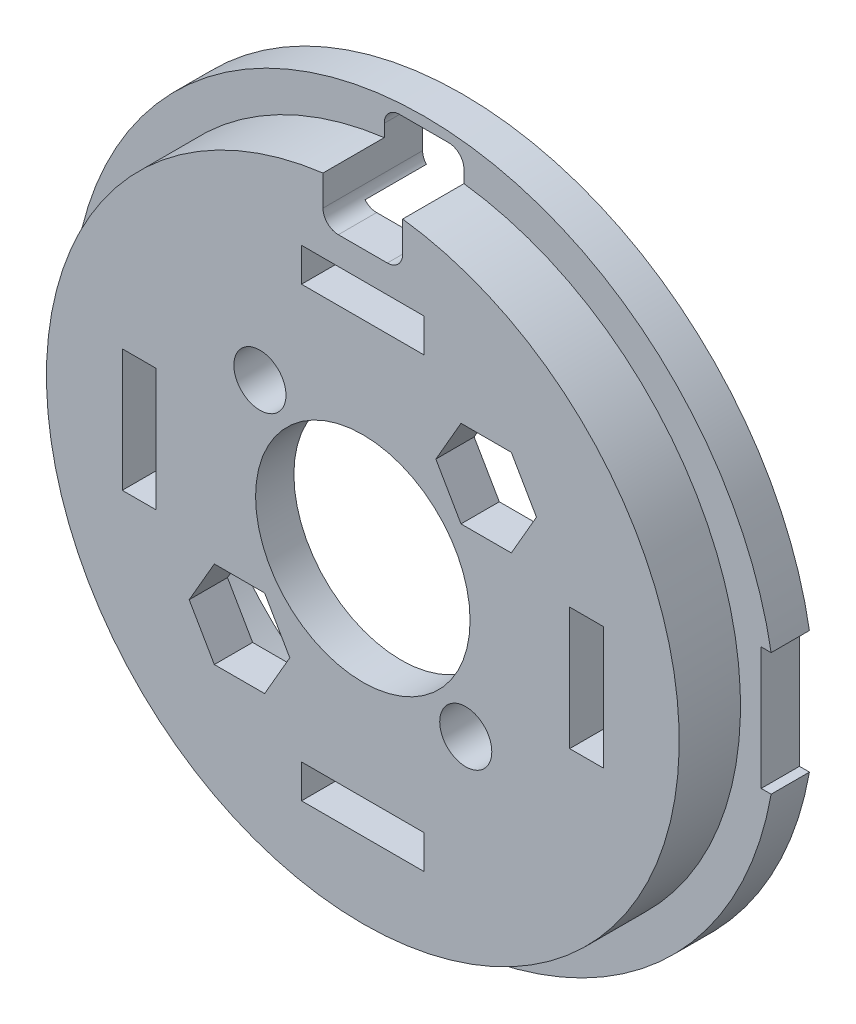
SolidWorks part; units mm, degrees
other "标注1"
sketch "草图10" plane through (17.4, 17.4, 7.6) normal (0.4476, 0.4282, 0.7851) x (0.8625, 0.025, -0.5054)
ref_plane "前视基准面" through (0, 0, 0) normal (0, 0, 1) x (1, 0, 0)
ref_plane "上视基准面" through (0, 0, 0) normal (0, 1, 0) x (1, 0, 0)
ref_plane "右视基准面" through (0, 0, 0) normal (1, 0, 0) x (0, 0, -1)
other "Configuration Table"
sketch "草图1" plane through (0, 0, 0) normal (0, 0, 1) x (1, 0, 0)
  circle A0 centre (0, 0) radius 17.4
  dimension "D1" = 34.8
extrude "凸台-拉伸1" add sketch "草图1" along normal blind 5.6
sketch "草图2" plane through (0, 0, 5.6) normal (0, 0, 1) x (1, 0, 0)
  line L0 (5.5154, -5.5154) -> (6.7175, -6.7175) construction
  line L1 (-6.7175, 6.7175) -> (-5.0175, 6.7175)
  line L2 (-6.7175, 6.7175) -> (-6.7175, 5.0175)
  line L3 (5.0175, -6.7175) -> (6.7175, -6.7175)
  line L4 (6.7175, -5.0175) -> (6.7175, -6.7175)
  line L5 (-6.7175, 6.7175) -> (-0.0325, 0.0325) construction
  line L6 (-6.7175, 6.7175) -> (6.7175, -6.7175)
  circle A0 centre (-6.7175, 6.7175) radius 1.7
  circle A2 centre (6.7175, -6.7175) radius 1.7
  arc A4 (-5.5154, -5.5154) -> (-6.7175, -5.0175) centre (-6.7175, -6.7175) ccw [skipped]
  arc A5 (5.0175, 6.7175) -> (5.5154, 5.5154) centre (6.7175, 6.7175) ccw [skipped]
  point P0 (0, 0)
  point P16 (0, 0)
  dimension "D3" = 3.4
  dimension "D1" = 19
  dimension "D2" = 9.5
  dimension "D4" = 4
extrude "切除-拉伸1" cut sketch "草图2" against normal through all contours A0 | A2
sketch "草图3" plane through (0, 0, 5.6) normal (0, 0, 1) x (1, 0, 0)
  circle A0 centre (0, 0) radius 7
  dimension "D1" = 14
extrude "切除-拉伸2" cut sketch "草图3" against normal through all
sketch "草图4" plane through (0, 0, 5.6) normal (0, 0, 1) x (1, 0, 0)
  circle A1 centre (-6.7175, 6.7175) radius 2.8
  circle A2 centre (6.7175, -6.7175) radius 2.8
  dimension "D1" = 5.6
  dimension "D2" = 5.6
extrude "切除-拉伸3" cut sketch "草图4" against normal blind 3
sketch "草图5" plane through (0, 0, 5.6) normal (0, 0, 1) x (1, 0, 0)
  line L1 (-8.05, 8) -> (8.05, 8)
  line L2 (-8.05, 8) -> (-8.05, -8)
  line L3 (-8.05, -8) -> (8.05, -8)
  line L4 (8.05, 8) -> (8.05, -8)
  line L5 (-8.05, 8) -> (8.05, -8) construction
  line L6 (-8.05, -8) -> (8.05, 8) construction
  circle A0 centre (8.05, 8) radius 1.7
  circle A1 centre (-8.05, -8) radius 1.7
  point P0 (0, 0)
  dimension "D3" = 3.4
  dimension "D4" = 3.4
  dimension "D1" = 16.1
  dimension "D2" = 16
extrude "切除-拉伸4" cut sketch "草图5" against normal through all contours A1 | A0
sketch "草图6" plane through (0, 0, 0) normal (0, 0, -1) x (-1, 0, 0)
  line L0 (4.7668, -8) -> (6.4084, -10.8433)
  line L1 (-4.7668, 8) -> (-6.4084, 10.8433)
  line L2 (-6.4084, 10.8433) -> (-9.6916, 10.8433)
  line L3 (-9.6916, 10.8433) -> (-11.3332, 8)
  line L4 (-11.3332, 8) -> (-9.6916, 5.1567)
  line L5 (-9.6916, 5.1567) -> (-6.4084, 5.1567)
  line L6 (-6.4084, 5.1567) -> (-4.7668, 8)
  line L7 (6.4084, -10.8433) -> (9.6916, -10.8433)
  line L8 (9.6916, -10.8433) -> (11.3332, -8)
  line L9 (11.3332, -8) -> (9.6916, -5.1567)
  line L10 (9.6916, -5.1567) -> (6.4084, -5.1567)
  line L11 (6.4084, -5.1567) -> (4.7668, -8)
  circle A0 centre (-8.05, 8) radius 2.8433 construction
  point P17 (0, 0)
  dimension "D1" = 2
extrude "切除-拉伸5" cut sketch "草图6" against normal blind 2.5
sketch "草图7" plane through (0, 0, 5.6) normal (0, 0, 1) x (1, 0, 0)
  line L5 (-8.05, 8.05) -> (8.05, 8.05)
  line L6 (-8.05, 8.05) -> (-8.05, -8.05)
  line L11 (-8.05, -8.05) -> (8.05, -8.05)
  line L12 (8.05, 8.05) -> (8.05, -8.05)
  line L13 (-8.05, 8.05) -> (8.05, -8.05) construction
  line L14 (-8.05, -8.05) -> (8.05, 8.05) construction
  point P0 (0, 0)
  dimension "D1" = 16.1
  dimension "D2" = 16.1
extrude "切除-拉伸6" cut sketch "草图7" against normal blind 1.5
chamfer "倒角1" distance 0.5 angle 45 4 edges at (1.0479, 8.05, 5.6) (8.05, 1.0226, 5.6) (-1.0479, -8.05, 5.6) (-8.05, -1.0226, 5.6)
sketch "草图8" plane through (0, 0, 0) normal (1, 0, 0) x (0, 0, -1)
  line L0 (0, 17.4) -> (0, 17.2)
  line L1 (0, 17.4) -> (0.2, 17.4)
  line L2 (0.2, 17.4) -> (0, 17.2)
  dimension "D1" = 0.2
  dimension "D2" = 0.2
ref_axis "基准轴1" through (0, 0, 0) along (0, 0, 1)
revolve "旋转1" add sketch "草图8" angle 360 about axis through (0, 0, 0) along (0, 0, 1)
sketch "草图9" plane through (0, 0, 5.6) normal (0, 0, 1) x (1, 0, 0)
  line L0 (0, 0) -> (15, 0) construction
  line L1 (4, -13.5) -> (-4, -13.5)
  line L2 (13.5, 4) -> (16.5, 4)
  line L3 (13.5, 4) -> (13.5, -4)
  line L4 (13.5, -4) -> (16.5, -4)
  line L5 (16.5, 4) -> (16.5, -4)
  line L6 (13.5, 4) -> (16.5, -4) construction
  line L7 (13.5, -4) -> (16.5, 4) construction
  line L8 (4, -13.5) -> (4, -16.5)
  line L9 (4, -16.5) -> (-4, -16.5)
  line L10 (-4, -13.5) -> (-4, -16.5)
  line L11 (-13.5, -4) -> (-13.5, 4)
  line L12 (-13.5, -4) -> (-16.5, -4)
  line L13 (-16.5, -4) -> (-16.5, 4)
  line L14 (-13.5, 4) -> (-16.5, 4)
  line L15 (-4, 13.5) -> (4, 13.5)
  line L16 (-4, 13.5) -> (-4, 16.5)
  line L17 (-4, 16.5) -> (4, 16.5)
  line L18 (4, 13.5) -> (4, 16.5)
  line L19 (15.7, 4) -> (15.7, -4)
  line L20 (4, -15.7) -> (-4, -15.7)
  line L21 (-15.7, -4) -> (-15.7, 4)
  line L22 (-4, 15.7) -> (4, 15.7)
  point P22 (0, 0)
  point P31 (0, 0)
  dimension "D1" = 15
  dimension "D2" = 3
  dimension "D3" = 8
  dimension "D5" = 0.8
  dimension "D4" = 4
  dimension "D6" = 4
extrude "切除-拉伸7" cut sketch "草图9" against normal through all contours L19 L2 L3 L4 | L22 L16 L15 L18 | L21 L12 L11 L14 | L20 L8 L1 L10 region at (0, -14.6, 5.6) region at (14.6, 0, 5.6) region at (-14.6, 0, 5.6) region at (0, 14.6, 5.6)
sketch "Sketch1" plane through (0, 0, 0) normal (0, 0, 1) x (1, 0, 0)
  circle A0 centre (0, 0) radius 17.4
  circle A1 centre (0, 0) radius 20.65
  dimension "D1" = 41.3
extrude "Boss-Extrude1" add sketch "Sketch1" along normal up to surface (5.6 mm away) and the other way blind 4 up to face at (0, 0, 5.6)
sketch "Sketch2" plane through (0, 0, -4) normal (0, 0, -1) x (-1, 0, 0)
  line L0 (0, 0) -> (-17.5, 0)
  line L1 (-17.5, 0) -> (-17.5, 4)
  line L2 (-17.5, 4) -> (-20, 4)
  line L3 (-20, 4) -> (-20, -4)
  line L4 (-20, -4) -> (-17.5, -4)
  line L5 (-17.5, -4) -> (-17.5, 0)
  dimension "D1" = 2.5
  dimension "D2" = 4
  dimension "D3" = 4
  dimension "D4" = 17.5
sketch "Sketch3" plane through (0, 0, -4) normal (0, 0, -1) x (-1, 0, 0)
  circle A0 centre (0, 0) radius 20.65
  circle A1 centre (0, 0) radius 23
  circle M10 centre (0, 0) radius 20.65
  dimension "D1" = 46
extrude "Boss-Extrude2" add sketch "Sketch3" against normal blind 2.5 contours A1 M10 region at (22.3495, 0, -4)
sketch "Sketch4" plane through (0, 0, -4) normal (0, 0, -1) x (-1, 0, 0)
  circle A0 centre (0, 0) radius 18
  dimension "D1" = 36
extrude "Cut-Extrude3" cut sketch "Sketch4" against normal up to surface (4 mm away) up to face at (0, 14.6, 0)
sketch "Sketch5" plane through (0, 0, -4) normal (0, 0, -1) x (-1, 0, 0)
  line L13 (0, 0) -> (23, 0)
  line L14 (0, 0) -> (-23, 0)
  line L15 (23, -4) -> (22, -4)
  line L16 (23, -4) -> (23, 4)
  line L17 (23, 4) -> (22, 4)
  line L18 (22, -4) -> (22, 4)
  line L19 (-23, 4) -> (-22, 4)
  line L20 (-23, 4) -> (-23, -4)
  line L21 (-23, -4) -> (-22, -4)
  line L22 (-22, 4) -> (-22, -4)
  circle A0 centre (0, 0) radius 23 construction
  point P9 (0, 22)
  point P19 (0, -22)
  point P23 (0, 0)
  point P34 (0, 0)
  dimension "D4" = 8
  dimension "D5" = 1
  dimension "D6" = 4
  dimension "D3" = 2
  dimension "D7" = 2
extrude "Cut-Extrude4" cut sketch "Sketch5" against normal blind 10 contours L19 L22 L21 L20 | L16 L15 L18 L17
sketch "Sketch7" plane through (0, 0, -4) normal (0, 0, -1) x (-1, 0, 0)
  line L1 (0, 22.3) -> (2.6, 22.3)
  line L2 (0, 17.5) -> (-2.6, 17.5)
  line L3 (0, 17.5) -> (0, 22.3)
  line L4 (0, 22.3) -> (-2.6, 22.3)
  line L5 (-2.6, 17.5) -> (-2.6, 22.3)
  line L7 (0, 22.3) -> (0, 17.5)
  line L10 (0, 22.3) -> (0, 17.5)
  line L11 (0, 17.5) -> (2.6, 17.5)
  line L12 (2.6, 22.3) -> (2.6, 17.5)
  circle M5 centre (0, 0) radius 18
  dimension "D1" = 2.6
  dimension "D2" = 2.6
  dimension "D3" = 4.8
extrude "Cut-Extrude6" cut sketch "Sketch7" against normal blind 10 contours L5 L3 L4 M5 | L5 L2 L3 M5 | L12 L1 L3 M5 | L12 L3 L11 M5 region at (-1.3094, 20.1182, -4) region at (1.3094, 20.1182, -4) region at (-1.2066, 17.7222, -4) region at (1.2066, 17.7222, -4)
fillet "Fillet3" radius 1 4 edges at (2.6, 22.3, -2.75) (-2.6, 22.3, -2.75) (-2.6, 17.5, 2.8) (2.6, 17.5, 2.8)
sketch "Sketch8" plane through (0, 0, 5.6) normal (0, 0, 1) x (1, 0, 0)
  circle A0 centre (0, 0) radius 23
sketch "Sketch9" plane through (0, 0, -4) normal (0, 0, -1) x (-1, 0, 0)
  circle A0 centre (0, 0) radius 23
sketch "Sketch10" plane through (0, 0, 5.6) normal (0, 0, 1) x (1, 0, 0)
  circle A0 centre (0, 0) radius 23
extrude "Cut-Extrude7" cut sketch "Sketch10" against normal up to surface (3.1 mm away) up to face at (8.05, 8, 2.5)
